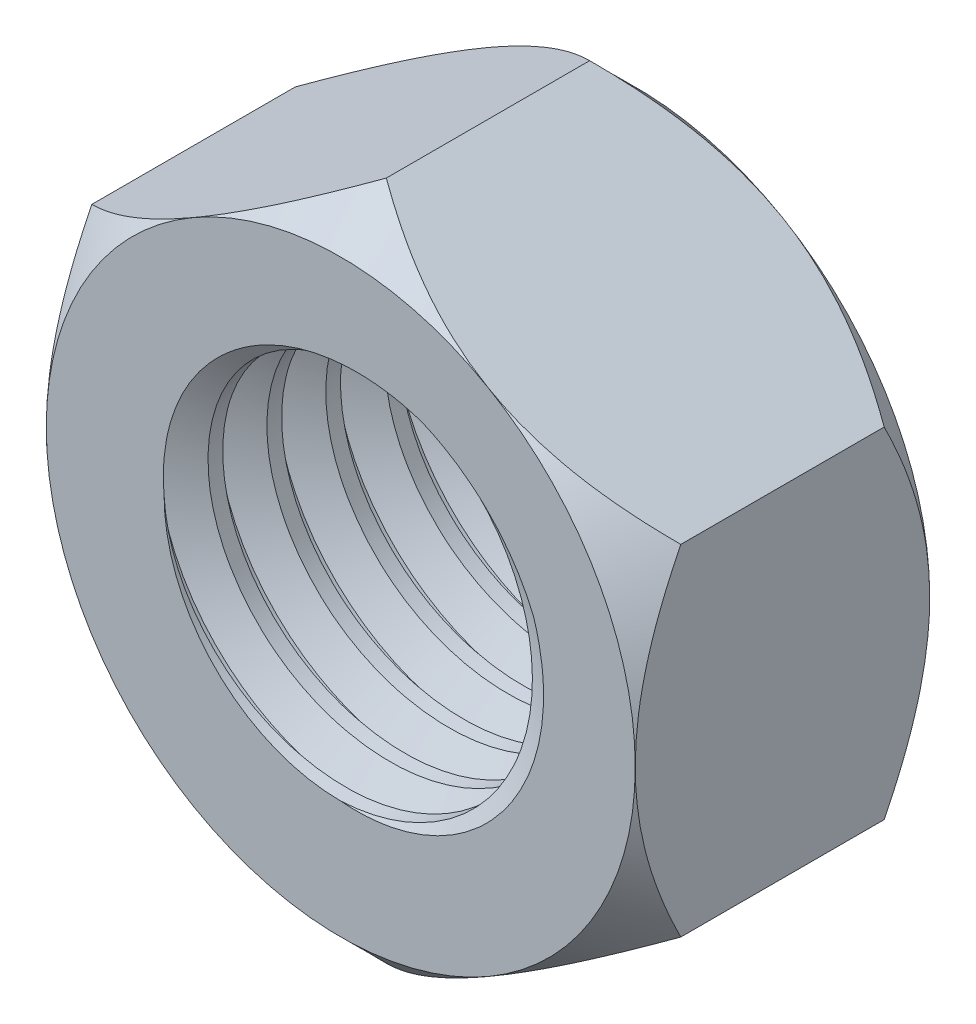
SolidWorks part; units mm, degrees
ref_plane "Front Plane" through (0, 0, 0) normal (0, 0, 1) x (1, 0, 0)
ref_plane "Top Plane" through (0, 0, 0) normal (0, 1, 0) x (1, 0, 0)
ref_plane "Right Plane" through (0, 0, 0) normal (1, 0, 0) x (0, 0, -1)
sketch "Sketch1" plane through (0, 0, 0) normal (0, 0, 1) x (1, 0, 0)
  line L1 (5, -2.8868) -> (5, 2.8868)
  line L2 (5, 2.8868) -> (0, 5.7735)
  line L3 (0, 5.7735) -> (-5, 2.8868)
  line L4 (-5, 2.8868) -> (-5, -2.8868)
  line L5 (-5, -2.8868) -> (0, -5.7735)
  line L6 (0, -5.7735) -> (5, -2.8868)
  circle A0 centre (0, 0) radius 5 construction
  circle A1 centre (0, 0) radius 3
  dimension "D1" = 10
  dimension "D2" = 6
extrude "Boss-Extrude2" add sketch "Sketch1" along normal mid plane 5 contours A1 | L5 L6 L1 L2 L3 L4 A1
sketch "Sketch2" plane through (0, 0, 2.5) normal (0, 0, 1) x (1, 0, 0)
  circle A0 centre (0, 0) radius 3
  dimension "D1" = 6
sketch "Sketch3" plane through (0, 0, 2.5) normal (0, 0, 1) x (1, 0, 0)
  circle A0 centre (0, 0) radius 5
extrude "Cut-Extrude1" cut sketch "Sketch2" against normal through all and the other way through all
extrude "Cut-Extrude2" cut sketch "Sketch3" against normal blind 10 draft 45 flip side to cut
mirror "Mirror1" about plane through (0, 0, 0) normal (0, 0, 1) of "Cut-Extrude2"
thread "Thread1" start angle 0, offset 2, length 10, pitch 1, diameter 6
ref_plane "Plane1" through (-3, 0, 4.5) normal (0, -1, 0) x (-1, 0, 0)
sketch "Thread Profile1" plane through (-3, 0, 4.5) normal (0, -1, 0) x (-1, 0, 0)
  line L0 (0, 0) -> (0, 1) construction
  line L1 (0, 0) -> (0.5413, 0.3125)
  line L2 (0.5413, 0.3125) -> (0.5413, 0.4375)
  line L3 (0.5413, 0.4375) -> (0, 0.75)
  line L4 (0.5413, 0.375) -> (0, 0.375) construction
  line L11 (0, 0) -> (0, 0.75)
  point P2 (0, 0)
  dimension "Pitch" = 1
  dimension "Profile_Angle" = 60
  dimension "Profile_Land" = 0.125
  dimension "Profile_Height" = 0.5413
